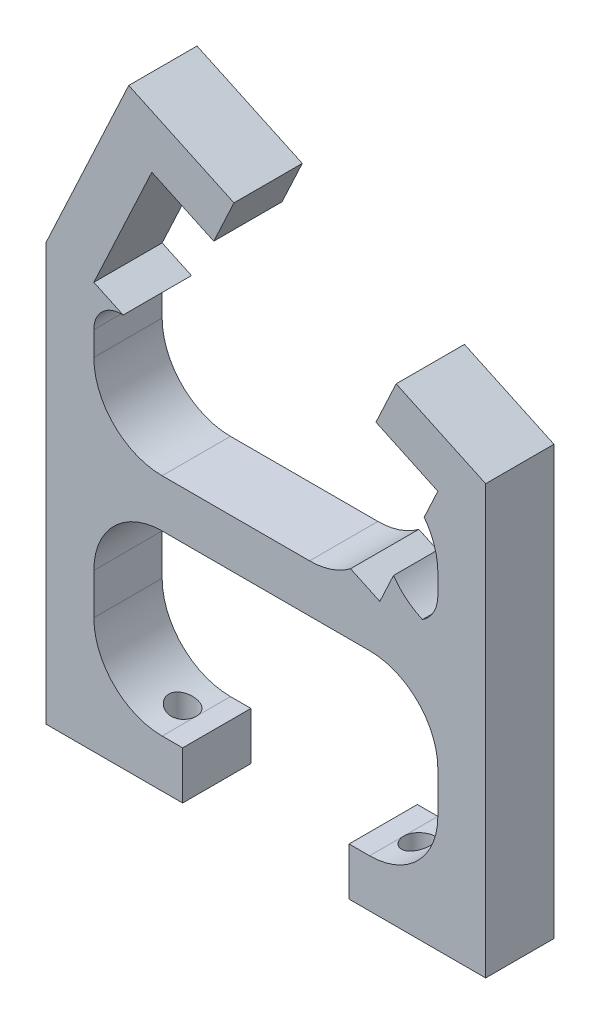
SolidWorks part; units mm, degrees
ref_plane "Alzado" through (0, 0, 0) normal (0, 0, 1) x (1, 0, 0)
ref_plane "Planta" through (0, 0, 0) normal (0, 1, 0) x (1, 0, 0)
ref_plane "Vista lateral" through (0, 0, 0) normal (1, 0, 0) x (0, 0, -1)
sketch "Croquis1" plane through (0, 0, 0) normal (0, 0, 1) x (1, 0, 0)
  line L0 (-15.183, 0) -> (15.183, 0)
  line L1 (-25.183, -10) -> (-25.183, -16)
  line L2 (-25.183, -33) -> (-32.183, -33)
  line L3 (-32.183, -33) -> (-32.183, 7)
  line L4 (-16.6884, 44.7418) -> (25.183, 25.2168) construction
  line L5 (25.183, 25.2168) -> (16.6884, 7) construction
  line L6 (16.6884, 7) -> (-25.183, 26.525) construction
  line L7 (-25.183, 26.525) -> (-16.6884, 44.7418) construction
  line L8 (0, 0) -> (4.2473, 34.9793) construction
  line L9 (-25.183, 24.525) -> (-25.183, 7) construction
  line L10 (-25.183, 7) -> (12.3994, 7) construction
  line L11 (25.183, 20.9278) -> (25.183, 0) construction
  line L12 (25.183, 20.9278) -> (25.183, 12)
  line L13 (20.183, 7) -> (18.6884, 7)
  line L14 (-25.183, 17) -> (-25.183, 20.525)
  line L15 (0, 0) -> (0, 7) construction
  line L16 (-32.183, -0.1225) -> (-25.183, -0.1225) construction
  line L17 (-32.183, 7) -> (-25.183, 7) construction
  line L18 (-25.183, -33) -> (-12.183, -33)
  line L19 (-12.183, -33) -> (-12.183, -26)
  line L20 (-12.183, -26) -> (-15.183, -26)
  line L21 (-25.183, -26) -> (-25.183, -33) construction
  line L22 (25.183, -33) -> (32.183, -33)
  line L23 (25.183, -33) -> (12.183, -33)
  line L24 (12.183, -33) -> (12.183, -26)
  line L25 (12.183, -26) -> (15.183, -26)
  line L26 (32.183, -33) -> (32.183, 7)
  line L27 (25.183, -10) -> (25.183, -16)
  line L28 (25.183, 25.2168) -> (16.1199, 29.443)
  line L29 (16.1199, 29.443) -> (19.0783, 35.7871)
  line L30 (19.0783, 35.7871) -> (32.183, 29.6763)
  line L31 (32.183, 29.6763) -> (32.183, 7)
  line L32 (20.6515, 27.3299) -> (23.6098, 33.674) construction
  line L33 (-32.183, 7) -> (-32.183, 28.0768)
  line L34 (-32.183, 28.0768) -> (-20.0742, 54.0442)
  line L35 (-20.0742, 54.0442) -> (-4.667, 46.8597)
  line L36 (-4.667, 46.8597) -> (-7.6253, 40.5156)
  line L37 (-7.6253, 40.5156) -> (-16.6884, 44.7418)
  line L38 (-16.6884, 44.7418) -> (-25.183, 26.525)
  line L39 (-26.1286, 41.0605) -> (-19.7845, 38.1022) construction
  line L40 (-12.1569, 42.6287) -> (-9.1985, 48.9728) construction
  line L41 (25.183, 25.2168) -> (23.183, 20.9278)
  line L42 (23.183, 20.9278) -> (25.183, 20.9278)
  line L43 (-21.183, 24.525) -> (-20.894, 24.525)
  line L44 (-25.183, 26.525) -> (-20.894, 24.525)
  line L45 (12.3994, 9) -> (12.3994, 7)
  line L47 (18.6884, 7) -> (18.6884, 11.289)
  line L48 (18.6884, 11.289) -> (16.6884, 7)
  line L49 (16.6884, 7) -> (12.3994, 9)
  line L50 (12.3994, 7) -> (-15.183, 7)
  arc A0 (15.183, -26) -> (25.183, -16) centre (15.183, -16) ccw
  arc A1 (-15.183, -26) -> (-25.183, -16) centre (-15.183, -16) cw
  arc A2 (15.183, 0) -> (25.183, -10) centre (15.183, -10) cw
  arc A3 (-15.183, 0) -> (-25.183, -10) centre (-15.183, -10) ccw
  arc A4 (-15.183, 7) -> (-25.183, 17) centre (-15.183, 17) cw
  arc A5 (-21.183, 24.525) -> (-25.183, 20.525) centre (-21.183, 20.525) ccw
  arc A6 (25.183, 12) -> (20.183, 7) centre (20.183, 12) cw
  point P4 (0, 0)
  point P16 (0, 7)
  point P52 (25.183, -26)
  point P61 (-25.183, 0)
  point P70 (25.183, 7)
  dimension "D13" = 10
  dimension "D14" = 4
  dimension "D15" = 5
  dimension "D1" = 7
  dimension "D2" = 20.1
  dimension "D3" = 46.2
  dimension "D4" = 25
  dimension "D5" = 40
  dimension "D6" = 20
  dimension "D7" = 10
  dimension "D8" = 10
  dimension "D9" = 2
  dimension "D10" = 2
  dimension "D11" = 2
  dimension "D12" = 2
extrude "Saliente-Extruir1" add sketch "Croquis1" along normal blind 10
fillet "Redondeo1" radius 10 2 edges at (18.6884, 7, 5) (12.3994, 7, 5)
fillet "Redondeo2" radius 10 1 edges at (25.183, 20.9278, 5)
sketch "Croquis2" plane through (0, -33, 0) normal (0, -1, 0) x (1, 0, 0)
  line L0 (-17.183, 5) -> (32.183, 5) construction
  line L1 (32.183, 10) -> (32.183, 0) construction
  line L2 (-12.183, 10) -> (-12.183, 0) construction
  line L3 (12.183, 10) -> (12.183, 0) construction
  circle A0 centre (-17.183, 5) radius 2
  circle A1 centre (17.183, 5) radius 2
  dimension "D1" = 5
  dimension "D2" = 4
  dimension "D3" = 5
extrude "Cortar-Extruir1" cut sketch "Croquis2" against normal blind 10
